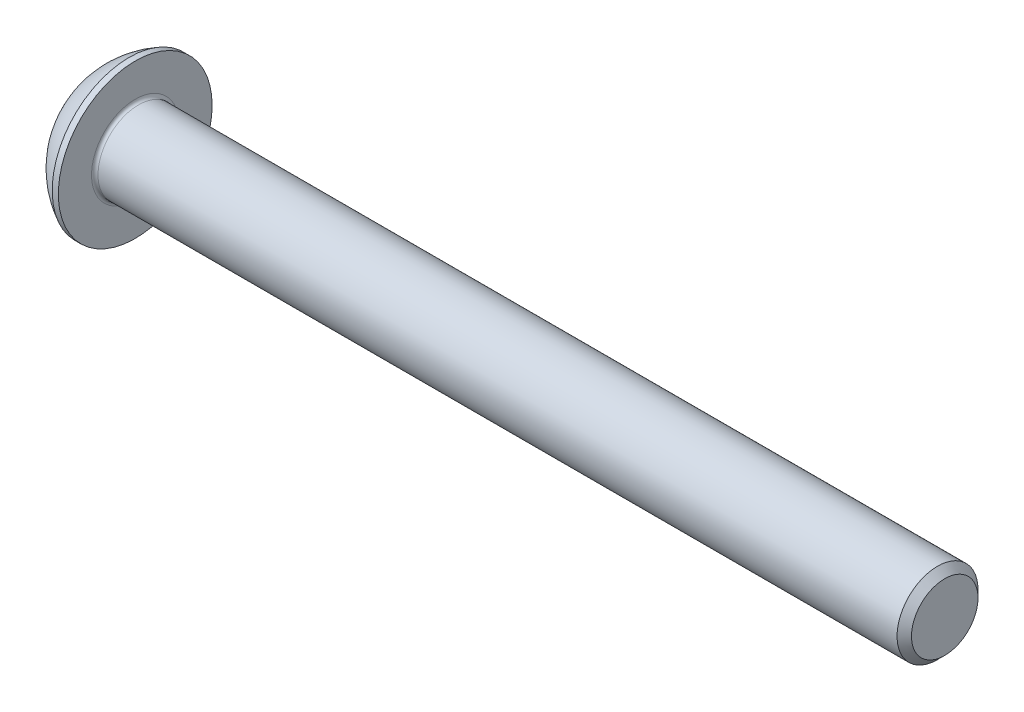
SolidWorks part; units mm, degrees
material "AISI 1020 Steel, Cold Rolled"
ref_plane "Спереди" through (0, 0, 0) normal (0, 0, 1) x (1, 0, 0)
ref_plane "Сверху" through (0, 0, 0) normal (0, 1, 0) x (1, 0, 0)
ref_plane "Справа" through (0, 0, 0) normal (1, 0, 0) x (0, 0, -1)
sketch "Эскиз1" plane through (0, 0, 0) normal (0, 0, 1) x (1, 0, 0)
  line L0 (-3.6435, 0) -> (-10.508, 0) construction
  line L1 (0, 2.375) -> (0, 0)
  line L2 (0, 0) -> (52.75, 0)
  line L3 (52.75, 0) -> (52.75, 2.055)
  line L4 (52.75, 2.055) -> (52.305, 2.5)
  line L5 (52.305, 2.5) -> (2.75, 2.5)
  line L6 (2.75, 2.5) -> (2.75, 4.75)
  line L7 (2.75, 4.75) -> (2.3702, 4.75)
  arc A0 (2.3702, 4.75) -> (0, 2.375) centre (4.7549, 0) ccw
  dimension "D1" = 10.63
  dimension "D2" = 4.75
  dimension "D3" = 2.75
  dimension "D4" = 5
  dimension "D5" = 45
  dimension "D6" = 4.11
  dimension "D7" = 50
  dimension "D8" = 9.5
revolve "Body" add sketch "Эскиз1" angle 360 about L0
fillet "Скругление1" radius 0.2 1 edges at (2.75, 0, -2.5)
sketch "Эскиз2" plane through (0, 0, 0) normal (0, 0, 1) x (1, 0, 0)
  line L0 (0, 0) -> (0, 1.5)
  line L1 (0, 2.375) -> (0, -2.375) construction
  line L2 (0, 1.5) -> (1.56, 1.5)
  line L3 (1.56, 1.5) -> (2.426, 0)
  line L4 (2.426, 0) -> (0, 0)
  dimension "D1" = 1.56
  dimension "D2" = 60
  dimension "D3" = 1.5
revolve "Вырез-Повернуть1" cut sketch "Эскиз2" angle 360 about L4
sketch "Эскиз3" plane through (0, 0, 0) normal (-1, 0, 0) x (0, 0, 1)
  line L1 (-1.5, -0.866) -> (0, -1.7321)
  line L2 (0, -1.7321) -> (1.5, -0.866)
  line L3 (1.5, -0.866) -> (1.5, 0.866)
  line L4 (1.5, 0.866) -> (0, 1.7321)
  line L5 (0, 1.7321) -> (-1.5, 0.866)
  line L6 (-1.5, 0.866) -> (-1.5, -0.866)
  circle A0 centre (0, 0) radius 1.5 construction
  dimension "D1" = 3
extrude "Hex" cut sketch "Эскиз3" against normal blind 1.56
